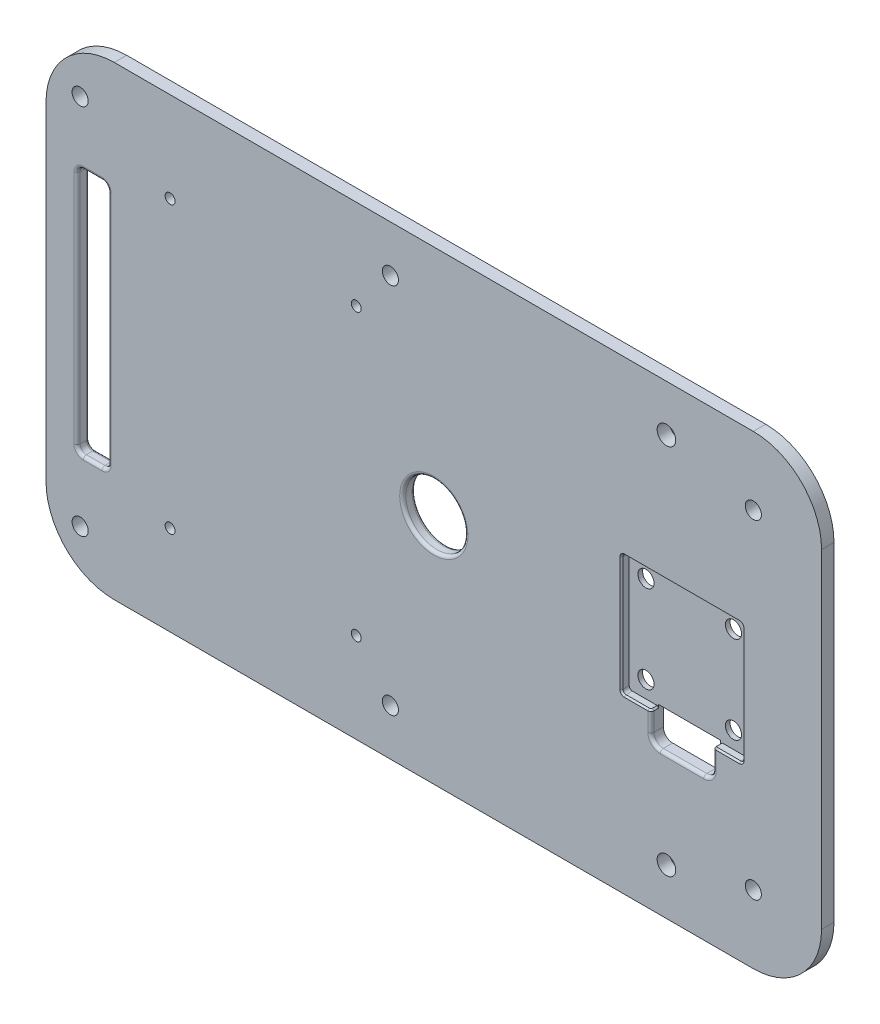
SolidWorks part; units mm, degrees
ref_plane "前视基准面" through (0, 0, 0) normal (0, 0, 1) x (1, 0, 0)
ref_plane "上视基准面" through (0, 0, 0) normal (0, 1, 0) x (1, 0, 0)
ref_plane "右视基准面" through (0, 0, 0) normal (1, 0, 0) x (0, 0, -1)
other "Configuration Table"
sketch "草图1" plane through (0, 0, 0) normal (0, 0, 1) x (1, 0, 0)
  line L0 (-1113.7626, 0) -> (48886.2374, 0) construction
  line L1 (-103, -75) -> (103, -75)
  line L2 (-125, -53) -> (-125, 53)
  line L3 (-103, 75) -> (103, 75)
  line L4 (125, -53) -> (125, 53)
  line L5 (-125, -75) -> (125, 75) construction
  line L6 (-125, 75) -> (125, -75) construction
  line L7 (-64, -1009.8705) -> (-64, 48990.1295) construction
  line L8 (-55, -1000) -> (-55, 49000) construction
  line L9 (-113, -40) -> (-107, -40)
  line L10 (-115, -38) -> (-115, 38)
  line L11 (-113, 40) -> (-107, 40)
  line L12 (-105, -38) -> (-105, 38)
  line L13 (-115, -40) -> (-105, 40) construction
  line L14 (-115, 40) -> (-105, -40) construction
  line L16 (-89, -50) -> (-21, -50) construction
  line L17 (-89, -50) -> (-89, 50) construction
  line L18 (-89, 50) -> (-21, 50) construction
  line L19 (-21, -50) -> (-21, 50) construction
  line L20 (-89, -50) -> (-21, 50) construction
  line L21 (-89, 50) -> (-21, -50) construction
  line L22 (70, -29) -> (90, -29)
  line L23 (70, -29) -> (70, -19)
  line L24 (70, -19) -> (90, -19)
  line L25 (90, -29) -> (90, -19)
  line L26 (70, -29) -> (90, -19) construction
  line L27 (70, -19) -> (90, -29) construction
  arc A0 (103, 75) -> (125, 53) centre (103, 53) cw
  arc A1 (103, -75) -> (125, -53) centre (103, -53) ccw
  arc A2 (-103, -75) -> (-125, -53) centre (-103, -53) cw
  arc A3 (-125, 53) -> (-103, 75) centre (-103, 53) cw
  circle A4 centre (-114, 60) radius 2.6
  circle A5 centre (-114, -60) radius 2.6
  circle A6 centre (-14, -60) radius 2.6
  circle A7 centre (-14, 60) radius 2.6
  arc A8 (-107, -40) -> (-105, -38) centre (-107, -38) ccw
  arc A9 (-113, -40) -> (-115, -38) centre (-113, -38) cw
  arc A10 (-105, 38) -> (-107, 40) centre (-107, 38) ccw
  arc A11 (-115, 38) -> (-113, 40) centre (-113, 38) cw
  circle A12 centre (-85, 46) radius 1.6
  circle A13 centre (-25, 46) radius 1.6
  circle A14 centre (-25, -46) radius 1.6
  circle A15 centre (-85, -46) radius 1.6
  circle A16 centre (103, 53) radius 2.6
  circle A17 centre (103, -53) radius 2.6
  circle A18 centre (0, 0) radius 10
  circle A19 centre (75, -60) radius 3
  circle A20 centre (75, 60) radius 3
  point P0 (0, 0)
  point P30 (-110, 0)
  point P57 (-55, 0)
  point P62 (80, -29)
  point P63 (80, -24)
  dimension "D3" = 22
  dimension "D4" = 5.2
  dimension "D6" = 11
  dimension "D7" = 15
  dimension "D8" = 120
  dimension "D12" = 2
  dimension "D13" = 3.2
  dimension "D14" = 92
  dimension "D15" = 60
  dimension "D23" = 5.2
  dimension "D24" = 20
  dimension "D25" = 50
  dimension "D26" = 15
  dimension "D1" = 150
  dimension "D2" = 250
  dimension "D5" = 50
  dimension "D9" = 10
  dimension "D10" = 10
  dimension "D11" = 80
  dimension "D16" = 70
  dimension "D17" = 68
  dimension "D18" = 100
  dimension "D19" = 20
  dimension "D20" = 10
  dimension "D21" = 24
  dimension "D22" = 70
extrude "凸台-拉伸1" add sketch "草图1" along normal blind 4
sketch "草图2" plane through (0, 0, 4) normal (0, 0, 1) x (1, 0, 0)
  line L0 (-1000, 0) -> (49000, 0) construction
  line L1 (60.5, -19.5) -> (99.5, -19.5)
  line L2 (60.5, -19.5) -> (60.5, 19.5)
  line L3 (60.5, 19.5) -> (99.5, 19.5)
  line L4 (99.5, -19.5) -> (99.5, 19.5)
  line L5 (60.5, -19.5) -> (99.5, 19.5) construction
  line L6 (60.5, 19.5) -> (99.5, -19.5) construction
  line L7 (0, -1000) -> (0, 49000) construction
  point P0 (80, 0)
  dimension "D1" = 39
  dimension "D2" = 39
  dimension "D3" = 80
extrude "切除-拉伸1" cut sketch "草图2" against normal blind 2.5
fillet "圆角1" radius 3 2 edges at (70, -29, 2) (90, -29, 2)
fillet "圆角2" radius 1 9 edges at (80, -29, 4) (70.8787, -28.1213, 4) (70, -22.75, 4) (60.5, -19.5, 2.75) (99.5, -19.5, 2.75) (99.5, 19.5, 2.75) (60.5, 19.5, 2.75) (89.1213, -28.1213, 4) (90, -22.75, 4)
chamfer "倒角1" distance 0.5 angle 45 10 edges at (60.7929, -19.2071, 4) (99.2071, -19.2071, 4) (99.5, 0, 4) (99.2071, 19.2071, 4) (80, 19.5, 4) (60.7929, 19.2071, 4) (60.5, 0, 4) (94.75, -19.5, 4) (90, -19.5, 2.25) (90.2929, -19.5, 3.7071)
sketch "草图4" plane through (0, 0, 1.5) normal (0, 0, 1) x (1, 0, 0)
  line L0 (61.5, -18.5) -> (98.5, 18.5) construction
  line L1 (61.5, 18.5) -> (98.5, -18.5) construction
  line L2 (-920, 0) -> (49080, 0) construction
  line L3 (80, -1000) -> (80, 49000) construction
  line L10 (60.5, 18.5) -> (60.5, -18.5)
  line L11 (61.5, -19.5) -> (69.5, -19.5)
  line L12 (69.5, -19.5) -> (70, -20)
  line L13 (70, -20) -> (70, -19)
  line L14 (70, -19) -> (90, -19)
  line L15 (90, -19) -> (90, -20)
  line L16 (90, -20) -> (90.5, -19.5)
  line L17 (90.5, -19.5) -> (98.5, -19.5)
  line L18 (99.5, -18.5) -> (99.5, 18.5)
  line L19 (98.5, 19.5) -> (61.5, 19.5)
  line L20 (60.5, 18.5) -> (60.5, -18.5) construction
  line L21 (61.5, -19.5) -> (69.5, -19.5) construction
  line L22 (69.5, -19.5) -> (70, -20) construction
  line L23 (70, -20) -> (70, -19) construction
  line L24 (70, -19) -> (90, -19) construction
  line L25 (90, -19) -> (90, -20) construction
  line L26 (90, -20) -> (90.5, -19.5) construction
  line L27 (90.5, -19.5) -> (98.5, -19.5) construction
  line L28 (99.5, -18.5) -> (99.5, 18.5) construction
  line L29 (98.5, 19.5) -> (61.5, 19.5) construction
  circle A0 centre (65.9003, -14.0997) radius 2.6
  circle A2 centre (94.0997, -14.0997) radius 2.6
  circle A3 centre (94.0997, 14.0997) radius 2.6
  arc A4 (60.5, -18.5) -> (61.5, -19.5) centre (61.5, -18.5) ccw
  arc A5 (98.5, -19.5) -> (99.5, -18.5) centre (98.5, -18.5) ccw
  arc A6 (99.5, 18.5) -> (98.5, 19.5) centre (98.5, 18.5) ccw
  arc A7 (61.5, 19.5) -> (60.5, 18.5) centre (61.5, 18.5) ccw
  arc A8 (60.5, -18.5) -> (61.5, -19.5) centre (61.5, -18.5) ccw construction
  arc A9 (98.5, -19.5) -> (99.5, -18.5) centre (98.5, -18.5) ccw construction
  arc A10 (99.5, 18.5) -> (98.5, 19.5) centre (98.5, 18.5) ccw construction
  arc A11 (61.5, 19.5) -> (60.5, 18.5) centre (61.5, 18.5) ccw construction
  circle A12 centre (65.9003, 14.0997) radius 2.6
  point P19 (80, 0)
  dimension "D2" = 5.2
  dimension "D3" = 39.88
  dimension "D1" = 0
extrude "切除-拉伸2" cut sketch "草图4" against normal blind 2
fillet "圆角3" radius 1 18 edges at (-114.4142, 39.4142, 0) (-110, 40, 0) (-105.5858, 39.4142, 0) (-105, 0, 0) (-105.5858, -39.4142, 0) (-110, -40, 0) (-114.4142, -39.4142, 0) (-114.4142, 39.4142, 4) (-110, 40, 4) (-105.5858, 39.4142, 4) (-105, 0, 4) (-105.5858, -39.4142, 4) (-110, -40, 4) (-114.4142, -39.4142, 4) (10, 0, 0) (10, 0, 4) (-115, 0, 0) (-115, 0, 4)
